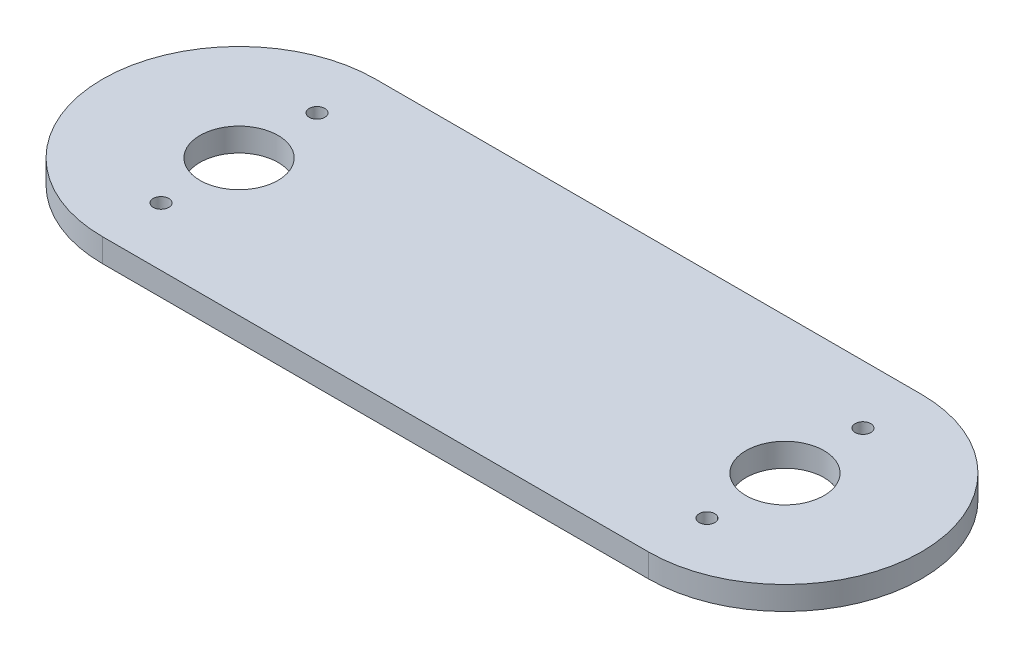
SolidWorks part; units mm, degrees
ref_plane "Front Plane" through (0, 0, 0) normal (0, 0, 1) x (1, 0, 0)
ref_plane "Top Plane" through (0, 0, 0) normal (0, 1, 0) x (1, 0, 0)
ref_plane "Right Plane" through (0, 0, 0) normal (1, 0, 0) x (0, 0, -1)
sketch "Sketch1" plane through (0, 0, 0) normal (0, 1, 0) x (1, 0, 0)
  line L0 (-31.9723, 0) -> (38.0277, 0)
  line L1 (38.0277, -35) -> (-31.9723, -35)
  arc A0 (38.0277, 0) -> (38.0277, -35) centre (38.0277, -17.5) cw
  arc A1 (-31.9723, -35) -> (-31.9723, 0) centre (-31.9723, -17.5) cw
  dimension "D1" = 70
  dimension "D2" = 35
extrude "Boss-Extrude1" add sketch "Sketch1" along normal blind 3
sketch "Sketch2" plane through (0, 3, 0) normal (0, 1, 0) x (1, 0, 0)
  line L0 (3.0277, -47.1371) -> (3.0277, 7.6363) construction
  line L1 (-31.9723, 0) -> (-31.9723, -35) construction
  line L2 (-54.6054, -17.5) -> (3.0277, -17.5) construction
  circle A0 centre (-31.9723, -17.5) radius 5
  circle A1 centre (-31.9723, -7.5) radius 1
  circle A2 centre (-31.9723, -27.5) radius 1
  circle A3 centre (38.0277, -7.5) radius 1
  circle A4 centre (38.0277, -17.5) radius 5
  circle A5 centre (38.0277, -27.5) radius 1
  dimension "D1" = 10
  dimension "D2" = 2
  dimension "D3" = 10
extrude "Cut-Extrude1" cut sketch "Sketch2" against normal through all
